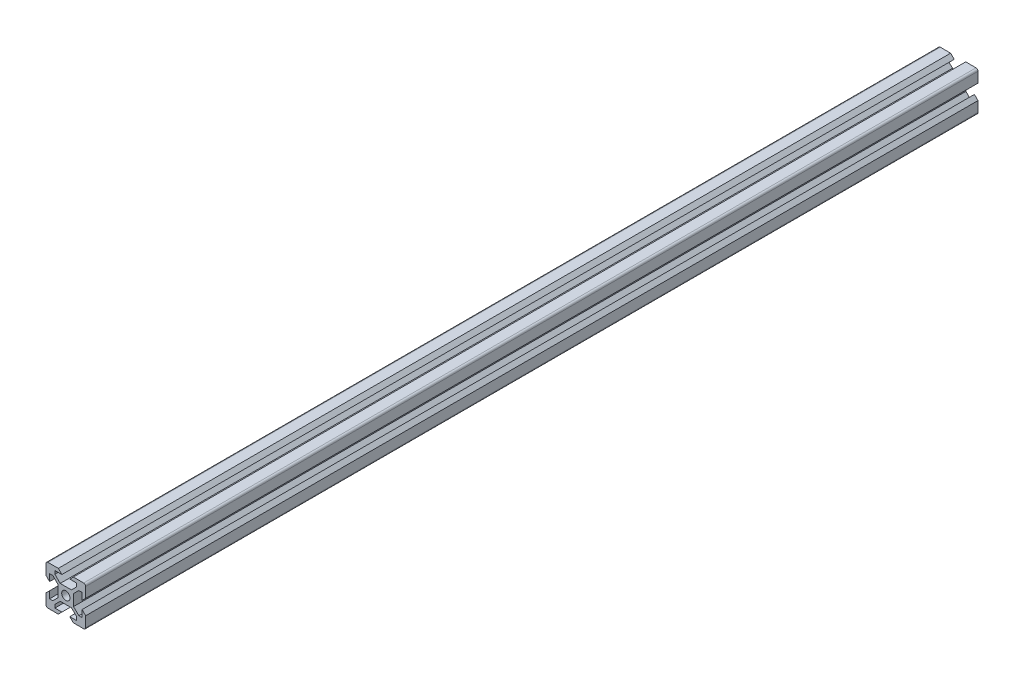
SolidWorks part; units mm, degrees
material "6063-T5"
ref_plane "Front Plane" through (0, 0, 0) normal (0, 0, 1) x (1, 0, 0)
ref_plane "Top Plane" through (0, 0, 0) normal (0, 1, 0) x (1, 0, 0)
ref_plane "Right Plane" through (0, 0, 0) normal (1, 0, 0) x (0, 0, -1)
sketch "Sketch1" plane through (0, 0, 0) normal (0, 0, 1) x (1, 0, 0)
  line L12 (-10, -10) -> (10, -10)
  line L17 (-10, -10) -> (-10, 10)
  line L18 (-10, 10) -> (10, 10)
  line L57 (10, -10) -> (10, 10)
  line L58 (-10, -10) -> (10, 10) construction
  line L59 (-10, 10) -> (10, -10) construction
  circle A1 centre (0, 0) radius 2.1
  dimension "D3" = 4.2
  dimension "D1" = 20
  dimension "D2" = 20
extrude "Boss-Extrude1" add sketch "Sketch1" along normal blind 450
sketch "Sketch2" plane through (0, 0, 0) normal (0, 0, -1) x (-1, 0, 0)
  line L0 (0, 0) -> (-3.9007, 0) construction
  line L1 (-3.9007, 2.84) -> (-3.9007, -2.84)
  line L2 (-3.9007, -2.84) -> (-6.56, -5.4993)
  line L3 (-8.2, -5.4993) -> (-8.2, -2)
  line L4 (-8.2, -2) -> (-10, -2)
  line L5 (-10, -10) -> (-10, 10) construction
  line L6 (-10, -2) -> (-10, 2)
  line L7 (-10, 2) -> (-8.2, 2)
  line L8 (-8.2, 2) -> (-8.2, 5.4993)
  line L9 (-6.56, 5.4993) -> (-3.9007, 2.84)
  line L10 (-6.56, 5.4993) -> (-8.2, 5.4993)
  line L11 (-6.56, -5.4993) -> (-8.2, -5.4993)
  line L12 (-3.9007, 0) -> (-10, 0) construction
  line L13 (0, 10) -> (0, -10) construction
  line L14 (-10, 10) -> (10, 10) construction
  line L15 (10, -10) -> (-10, -10) construction
  line L16 (0, 0) -> (-10, 10) construction
  line L17 (5.4993, 6.56) -> (2.84, 3.9007)
  line L18 (2.84, 3.9007) -> (-2.84, 3.9007)
  line L19 (5.4993, 6.56) -> (5.4993, 8.2)
  line L20 (2, 8.2) -> (5.4993, 8.2)
  line L21 (2, 10) -> (2, 8.2)
  line L22 (-2, 10) -> (2, 10)
  line L23 (-2, 8.2) -> (-2, 10)
  line L24 (-5.4993, 8.2) -> (-2, 8.2)
  line L25 (-5.4993, 6.56) -> (-5.4993, 8.2)
  line L26 (-2.84, 3.9007) -> (-5.4993, 6.56)
  line L27 (6.56, -5.4993) -> (3.9007, -2.84)
  line L28 (3.9007, -2.84) -> (3.9007, 2.84)
  line L29 (6.56, -5.4993) -> (8.2, -5.4993)
  line L30 (8.2, -2) -> (8.2, -5.4993)
  line L31 (10, -2) -> (8.2, -2)
  line L32 (10, 2) -> (10, -2)
  line L33 (8.2, 2) -> (10, 2)
  line L34 (8.2, 5.4993) -> (8.2, 2)
  line L35 (6.56, 5.4993) -> (8.2, 5.4993)
  line L36 (3.9007, 2.84) -> (6.56, 5.4993)
  line L37 (-5.4993, -6.56) -> (-2.84, -3.9007)
  line L38 (-2.84, -3.9007) -> (2.84, -3.9007)
  line L39 (-5.4993, -6.56) -> (-5.4993, -8.2)
  line L40 (-2, -8.2) -> (-5.4993, -8.2)
  line L41 (-2, -10) -> (-2, -8.2)
  line L42 (2, -10) -> (-2, -10)
  line L43 (2, -8.2) -> (2, -10)
  line L44 (5.4993, -8.2) -> (2, -8.2)
  line L45 (5.4993, -6.56) -> (5.4993, -8.2)
  line L46 (2.84, -3.9007) -> (5.4993, -6.56)
  point P57 (0, 0)
  dimension "D1" = 0.75
  dimension "D2" = 1.64
  dimension "D3" = 1.8
  dimension "D4" = 5.68
  dimension "D5" = 4
  dimension "D6" = 4
extrude "Cut-Extrude1" cut sketch "Sketch2" against normal through all
fillet "Fillet1" radius 1 4 edges at (10, -10, 225) (-10, -10, 225) (-10, 10, 225) (10, 10, 225)
chamfer "Chamfer1" distance 1.8 angle 45 8 edges at (10, 2, 225) (10, -2, 225) (2, -10, 225) (-2, -10, 225) (-10, -2, 225) (-10, 2, 225) (2, 10, 225) (-2, 10, 225)
